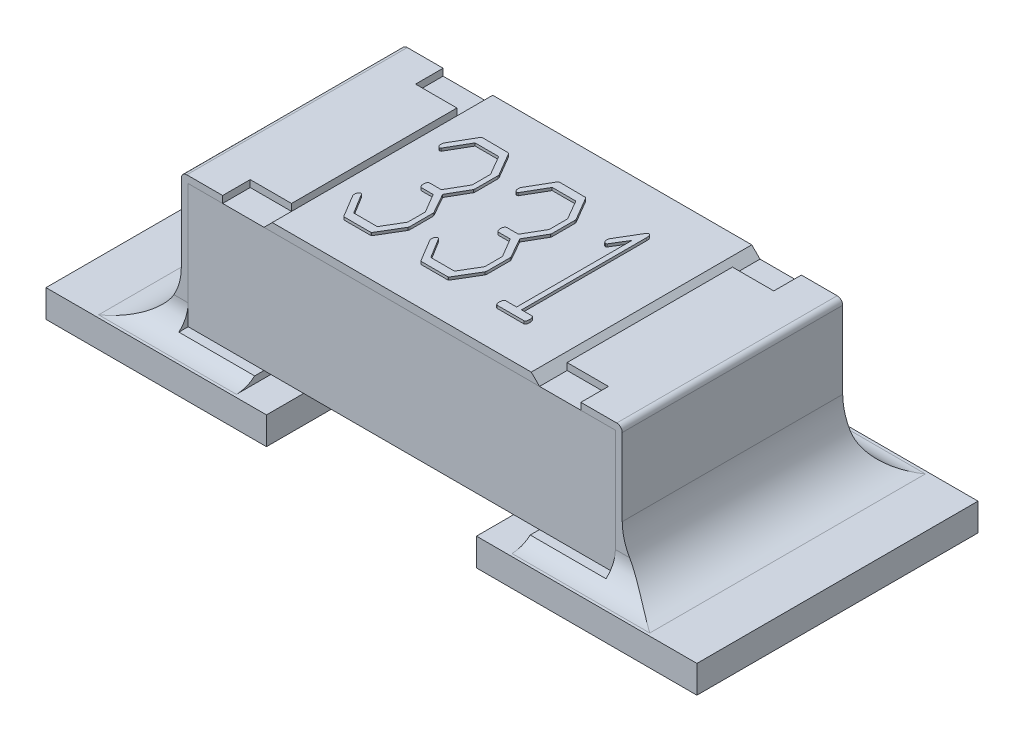
SolidWorks part; units mm, degrees
material "Ceramic Porcelain"
ref_plane "Front Plane" through (0, 0, 0) normal (0, 0, 1) x (1, 0, 0)
ref_plane "Top Plane" through (0, 0, 0) normal (0, 1, 0) x (1, 0, 0)
ref_plane "Right Plane" through (0, 0, 0) normal (1, 0, 0) x (0, 0, -1)
sketch "Sketch1" plane through (0, 0, 0) normal (1, 0, 0) x (0, 0, -1)
  line L0 (0, 55) -> (0, -55) construction
  line L1 (-0.4, 0.575) -> (0.4, 0.575)
  line L2 (-0.4, 0.575) -> (-0.4, 0.125)
  line L3 (-0.4, 0.125) -> (0.4, 0.125)
  line L4 (0.4, 0.575) -> (0.4, 0.125)
  line L5 (55, 0) -> (-55, 0) construction
  dimension "D1" = 0.8
  dimension "D2" = 0.4
  dimension "D3" = 0.45
  dimension "D4" = 0.125
extrude "Boss-Extrude1" add sketch "Sketch1" along normal mid plane 1.55
sketch "Sketch2" plane through (0, 0, 0) normal (0, 0, 1) x (1, 0, 0)
  line L0 (-0.5, 0.6) -> (-0.78, 0.6)
  line L1 (-0.8, 0.58) -> (-0.8, 0.1)
  line L2 (-0.8, 0.1) -> (-0.5, 0.1)
  line L3 (-0.5, 0.1) -> (-0.5, 0.125)
  line L4 (0.775, 0.125) -> (-0.775, 0.125) construction
  line L5 (-0.5, 0.125) -> (-0.775, 0.125)
  line L6 (-0.775, 0.125) -> (-0.775, 0.575)
  line L7 (-0.775, 0.575) -> (-0.5, 0.575)
  line L8 (0.775, 0.575) -> (-0.775, 0.575) construction
  line L9 (-0.5, 0.575) -> (-0.5, 0.6)
  line L11 (0.5, 0.575) -> (0.5, 0.6)
  line L12 (0.5, 0.6) -> (0.78, 0.6)
  line L13 (0.8, 0.58) -> (0.8, 0.1)
  line L14 (0.8, 0.1) -> (0.5, 0.1)
  line L15 (0.5, 0.1) -> (0.5, 0.125)
  line L16 (0.5, 0.125) -> (0.775, 0.125)
  line L17 (0.775, 0.125) -> (0.775, 0.575)
  line L18 (0.775, 0.575) -> (0.5, 0.575)
  arc A0 (0.78, 0.6) -> (0.8, 0.58) centre (0.78, 0.58) cw
  arc A1 (-0.78, 0.6) -> (-0.8, 0.58) centre (-0.78, 0.58) ccw
  point P28 (-0.8, 0.6)
  dimension "D6" = 0.02
  dimension "D1" = 0.025
  dimension "D2" = 0.025
  dimension "D3" = 0.025
  dimension "D4" = 0.3
  dimension "D5" = 0.3
extrude "Boss-Extrude2" add sketch "Sketch2" along normal mid plane 0.8 separate body
sketch "Sketch3" plane through (0, 0.6, 0) normal (0, 1, 0) x (1, 0, 0)
  line L0 (0.5, -0.4) -> (0.5, 0.4) construction
  line L1 (-0.5, 0.4) -> (-0.65, 0.4)
  line L2 (-0.5, 0.4) -> (-0.5, 0.3)
  line L3 (-0.5, 0.3) -> (-0.65, 0.3)
  line L4 (-0.65, 0.4) -> (-0.65, 0.3)
  line L5 (-0.5, -0.4) -> (-0.65, -0.4)
  line L6 (-0.5, -0.4) -> (-0.5, -0.3)
  line L7 (-0.5, -0.3) -> (-0.65, -0.3)
  line L8 (-0.65, -0.4) -> (-0.65, -0.3)
  line L9 (0.5, -0.4) -> (0.65, -0.4)
  line L10 (0.5, -0.4) -> (0.5, -0.3)
  line L11 (0.5, -0.3) -> (0.65, -0.3)
  line L12 (0.65, -0.4) -> (0.65, -0.3)
  line L13 (0.775, -0.4) -> (-0.775, -0.4) construction
  line L15 (0.5, 0.4) -> (0.65, 0.4)
  line L16 (0.5, 0.4) -> (0.5, 0.3)
  line L17 (0.5, 0.3) -> (0.65, 0.3)
  line L18 (0.65, 0.4) -> (0.65, 0.3)
  dimension "D1" = 0.15
  dimension "D2" = 0.1
extrude "Cut-Extrude1" cut sketch "Sketch3" against normal blind 0.025
sketch "Sketch4" plane through (0, 0, 0) normal (0, 0, 1) x (1, 0, 0)
  line L0 (-0.5, 0.575) -> (0.5, 0.575)
  line L1 (0.5, 0.575) -> (0.47, 0.605)
  line L2 (0.47, 0.605) -> (-0.47, 0.605)
  line L3 (-0.47, 0.605) -> (-0.5, 0.575)
  dimension "D1" = 45
  dimension "D2" = 45
  dimension "D3" = 0.03
extrude "Boss-Extrude3" add sketch "Sketch4" along normal mid plane 0.8 separate body
sketch "Sketch6" plane through (0, 0.605, 0) normal (0, 1, 0) x (1, 0, 0)
  line L0 (-0.4, -0.25) -> (0.4, -0.25) construction
  line L1 (0, -0.2777) -> (0, 0.2777) construction
  line L2 (-0.2777, 0) -> (0.2777, 0) construction
  text T0 "331\r\n" font "SWMono" height 0.5
  dimension "D1" = 0.8
  dimension "D2" = 0.4
  dimension "D3" = 0.25
extrude "Boss-Extrude4" add sketch "Sketch6" along normal blind 0.01
sketch "Sketch7" plane through (0, 0, 0) normal (0, 1, 0) x (1, 0, 0)
  line L0 (0, -0.2833) -> (0, 0.2833) construction
  line L1 (-0.381, -0.51) -> (-1.181, -0.51)
  line L2 (-0.381, -0.51) -> (-0.381, 0.51)
  line L3 (-0.381, 0.51) -> (-1.181, 0.51)
  line L4 (-1.181, -0.51) -> (-1.181, 0.51)
  line L5 (0.381, -0.51) -> (1.181, -0.51)
  line L6 (0.381, -0.51) -> (0.381, 0.51)
  line L7 (0.381, 0.51) -> (1.181, 0.51)
  line L8 (1.181, -0.51) -> (1.181, 0.51)
  line L9 (-0.2833, 0) -> (0.2833, 0) construction
  dimension "D1" = 0.8
  dimension "D2" = 0.381
  dimension "D3" = 0.381
  dimension "D4" = 1.02
  dimension "D5" = 0.51
extrude "Boss-Extrude5" add sketch "Sketch7" along normal blind 0.1
fillet "Fillet3" radius 0.2 1 edges at (-0.8, 0.1, 0)
fillet "Fillet4" radius 0.2 1 edges at (0.8, 0.1, 0)
fillet "Fillet5" radius 0.1 2 edges at (0.75, 0.1, -0.4) (0.75, 0.1, 0.4)
fillet "Fillet6" radius 0.1 2 edges at (-0.75, 0.1, 0.4) (-0.75, 0.1, -0.4)
